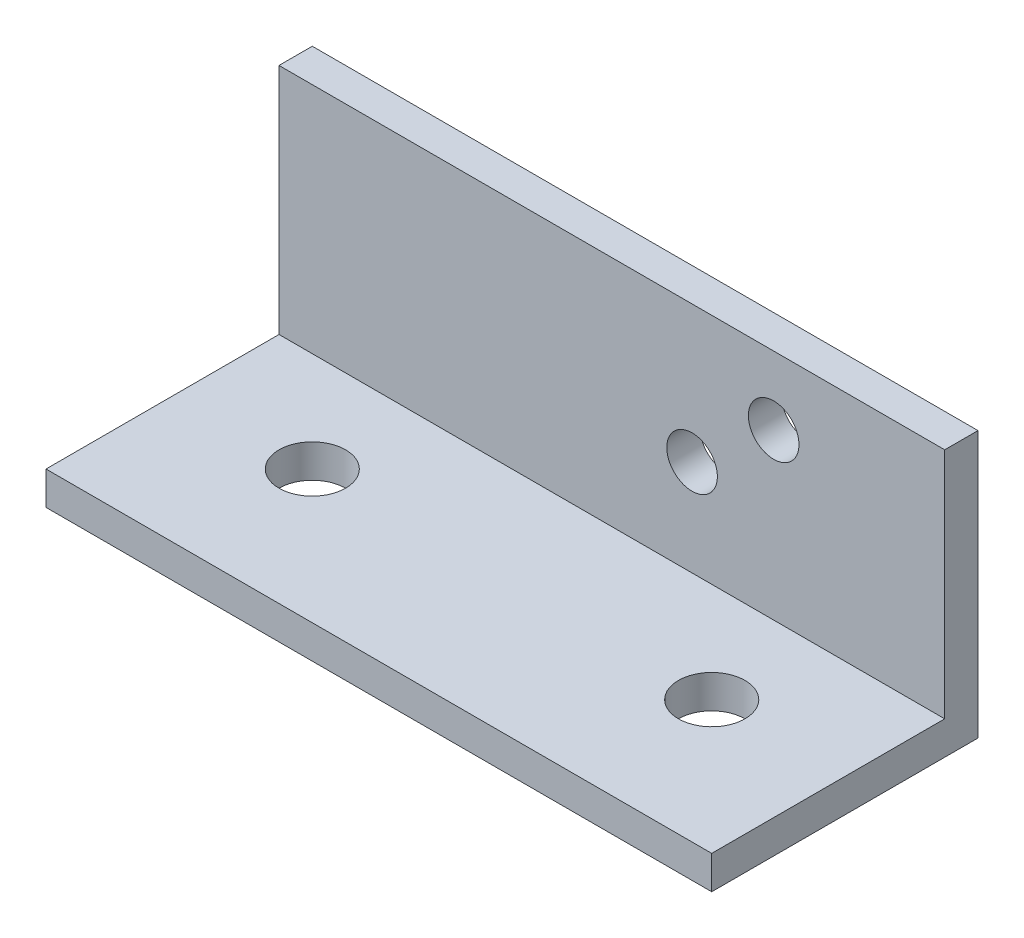
SolidWorks part; units mm, degrees
material "6061-T6 (SS)"
ref_plane "Front Plane" through (0, 0, 0) normal (0, 0, 1) x (1, 0, 0)
ref_plane "Top Plane" through (0, 0, 0) normal (0, 1, 0) x (1, 0, 0)
ref_plane "Right Plane" through (0, 0, 0) normal (1, 0, 0) x (0, 0, -1)
sketch "Sketch1" plane through (0, 0, 0) normal (0, 1, 0) x (1, 0, 0)
  line L1 (0, 0) -> (63.5, 0)
  line L2 (0, 0) -> (0, -25.4)
  line L3 (0, -25.4) -> (63.5, -25.4)
  line L4 (63.5, 0) -> (63.5, -25.4)
  dimension "D1" = 25.4
  dimension "D2" = 63.5
extrude "Boss-Extrude1" add sketch "Sketch1" along normal blind 3.175
sketch "Sketch2" plane through (0, 3.175, 0) normal (0, 1, 0) x (1, 0, 0)
  line L0 (63.5, -25.4) -> (63.5, 0) construction
  line L1 (0, 0) -> (63.5, 0)
  line L2 (0, 0) -> (0, -3.175)
  line L3 (0, -3.175) -> (63.5, -3.175)
  line L4 (63.5, 0) -> (63.5, -3.175)
  dimension "D1" = 3.175
extrude "Boss-Extrude2" add sketch "Sketch2" along normal blind 22.225
sketch "Sketch3" plane through (0, 3.175, 0) normal (0, 1, 0) x (1, 0, 0)
  line L1 (63.5, -25.4) -> (50.8, -25.4) construction
  line L2 (63.5, -25.4) -> (63.5, -12.7) construction
  line L3 (63.5, -12.7) -> (50.8, -12.7) construction
  line L4 (50.8, -25.4) -> (50.8, -12.7) construction
  line L5 (0, -25.4) -> (12.7, -25.4)
  line L6 (0, -25.4) -> (0, -12.7)
  line L7 (0, -12.7) -> (12.7, -12.7) construction
  line L8 (12.7, -25.4) -> (12.7, -12.7) construction
  circle A0 centre (12.7, -12.7) radius 3.175
  circle A1 centre (50.8, -12.7) radius 3.175
  dimension "D5" = 6.35
  dimension "D6" = 6.35
  dimension "D1" = 12.7
  dimension "D2" = 12.7
  dimension "D3" = 12.7
  dimension "D4" = 12.7
extrude "Cut-Extrude1" cut sketch "Sketch3" against normal blind 3.175 contours L3 A1 L4 | L4 A1 L3 | A0 region at (12.7, 3.175, 12.7) region at (50.8, 3.175, 12.7)
sketch "Sketch4" plane through (0, 0, 0) normal (0, 0, -1) x (-1, 0, 0)
  line L0 (-79.6648, 25.4) -> (-49.3942, 0) construction
  line L1 (-63.5, 0) -> (0, 0) construction
  line L2 (0, 25.4) -> (0, 0) construction
  line L3 (0, 0) -> (-30.2705, 25.4) construction
  line L4 (-63.5, 25.4) -> (0, 25.4) construction
  line L5 (-30.2705, 25.4) -> (-63.5, 25.4) construction
  line L6 (-33.2295, 0) -> (0, 0) construction
  line L7 (-79.6648, 25.4) -> (-30.2705, 25.4) construction
  line L8 (-54.9677, 25.4) -> (-24.6971, 0) construction
  circle A0 centre (-47.1846, 18.8693) radius 2.413
  circle A1 centre (-39.4016, 12.3386) radius 2.413
  dimension "D2" = 50
  dimension "D3" = 4.826
  dimension "D4" = 4.826
  dimension "D5" = 10.16
  dimension "D6" = 10.16
  dimension "D1" = 31.75
extrude "Cut-Extrude2" cut sketch "Sketch4" against normal blind 3.175
